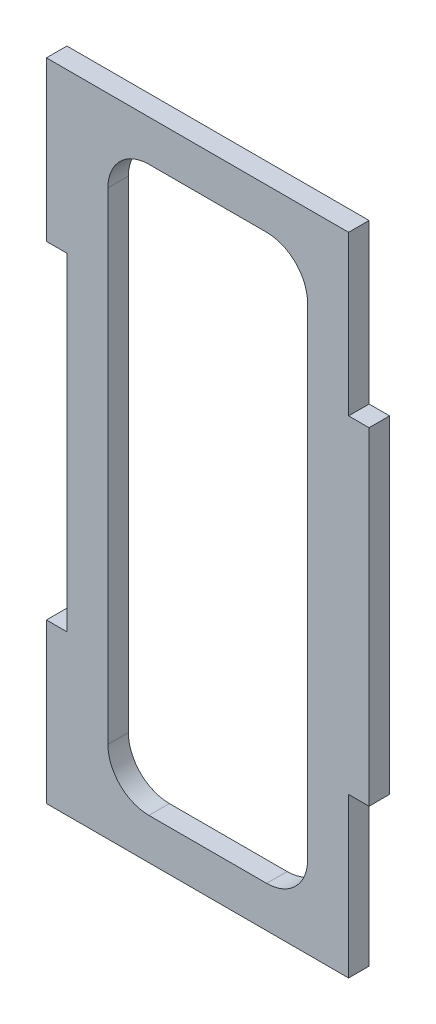
SolidWorks part; units mm, degrees
material "Acrylic (Medium-high impact)"
ref_plane "Front Plane" through (0, 0, 0) normal (0, 0, 1) x (1, 0, 0)
ref_plane "Top Plane" through (0, 0, 0) normal (0, 1, 0) x (1, 0, 0)
ref_plane "Right Plane" through (0, 0, 0) normal (1, 0, 0) x (0, 0, -1)
sketch "Sketch1" plane through (0, 0, 0) normal (0, 0, 1) x (1, 0, 0)
  line L1 (-50, -150.1518) -> (50, -150.1518)
  line L2 (-50, -150.1518) -> (-50, 50)
  line L3 (-50, 50) -> (50, 50)
  line L4 (50, -150.1518) -> (50, 50)
  dimension "D1" = 100
  dimension "D2" = 50
  dimension "D3" = 200.1518
  dimension "D4" = 50
extrude "Boss-Extrude1" add sketch "Sketch1" along normal blind 6.35
sketch "Sketch2" plane through (0, 0, 6.35) normal (0, 0, 1) x (1, 0, 0)
  line L0 (-43.65, 50) -> (-43.65, -150.1518) construction
  line L1 (50, 50) -> (-50, 50) construction
  line L2 (-50, -150.1518) -> (50, -150.1518) construction
  line L3 (-50, -50.0759) -> (50, -50.0759) construction
  line L4 (-50, 50) -> (-50, -150.1518) construction
  line L5 (50, -150.1518) -> (50, 50) construction
  line L6 (43.65, 50) -> (43.65, -150.1518) construction
  line L7 (-43.65, -50.0759) -> (-43.65, 50) construction
  line L8 (43.65, -50.0759) -> (43.65, 50) construction
  line L10 (-50, -50.0759) -> (-43.65, -50.0759)
  line L11 (-50, -50.0759) -> (-50, 0.7241)
  line L12 (-50, 0.7241) -> (-43.65, 0.7241)
  line L13 (-43.65, -50.0759) -> (-43.65, 0.7241)
  line L14 (-50, -50.0759) -> (-43.65, -50.0759)
  line L15 (-50, -50.0759) -> (-50, -100.8759)
  line L16 (-50, -100.8759) -> (-43.65, -100.8759)
  line L17 (-43.65, -50.0759) -> (-43.65, -100.8759)
  line L18 (43.65, 50) -> (50, 50)
  line L19 (43.65, 50) -> (43.65, 0.7241)
  line L20 (43.65, 0.7241) -> (50, 0.7241)
  line L21 (50, 50) -> (50, 0.7241)
  line L22 (43.65, -150.1518) -> (50, -150.1518)
  line L23 (43.65, -150.1518) -> (43.65, -100.8759)
  line L24 (43.65, -100.8759) -> (50, -100.8759)
  line L25 (50, -150.1518) -> (50, -100.8759)
  line M8 (-50, 50) -> (-50, -150.1518)
  line M9 (-50, -150.1518) -> (50, -150.1518)
  line M10 (50, -150.1518) -> (50, 50)
  line M11 (50, 50) -> (-50, 50)
  dimension "D1" = 6.35
  dimension "D2" = 6.35
  dimension "D3" = 100.0759
  dimension "D4" = 50.8
  dimension "D5" = 50.8
  dimension "D6" = 50.8
  dimension "D7" = 50.8
extrude "Cut-Extrude1" cut sketch "Sketch2" against normal blind 6.35 contours L10 L13 L12 M8 | L17 L10 L16 M8 | L19 L20 M10 M11 | L24 L23 M9 M10 region at (-46.825, -24.6759, 6.35) region at (-46.825, -75.4759, 6.35) region at (46.825, 25.3621, 6.35) region at (46.825, -125.5139, 6.35)
sketch "Sketch3" plane through (0, 0, 6.35) normal (0, 0, 1) x (1, 0, 0)
  line L0 (-43.65, -100.8759) -> (-43.65, 0.7241) construction
  line L1 (-30.95, -137.4518) -> (30.95, -137.4518)
  line L2 (-30.95, -137.4518) -> (-30.95, 37.3)
  line L3 (-30.95, 37.3) -> (30.95, 37.3)
  line L4 (30.95, -137.4518) -> (30.95, 37.3)
  line L5 (43.65, 50) -> (-50, 50) construction
  line L6 (43.65, 50) -> (43.65, 0.7241) construction
  line L7 (-50, -150.1518) -> (43.65, -150.1518) construction
  dimension "D1" = 12.7
  dimension "D2" = 12.7
  dimension "D3" = 12.7
  dimension "D4" = 12.7
extrude "Cut-Extrude2" cut sketch "Sketch3" against normal blind 6.35
fillet "Fillet1" radius 12.7 4 edges at (30.95, -137.4518, 3.175) (30.95, 37.3, 3.175) (-30.95, 37.3, 3.175) (-30.95, -137.4518, 3.175)
